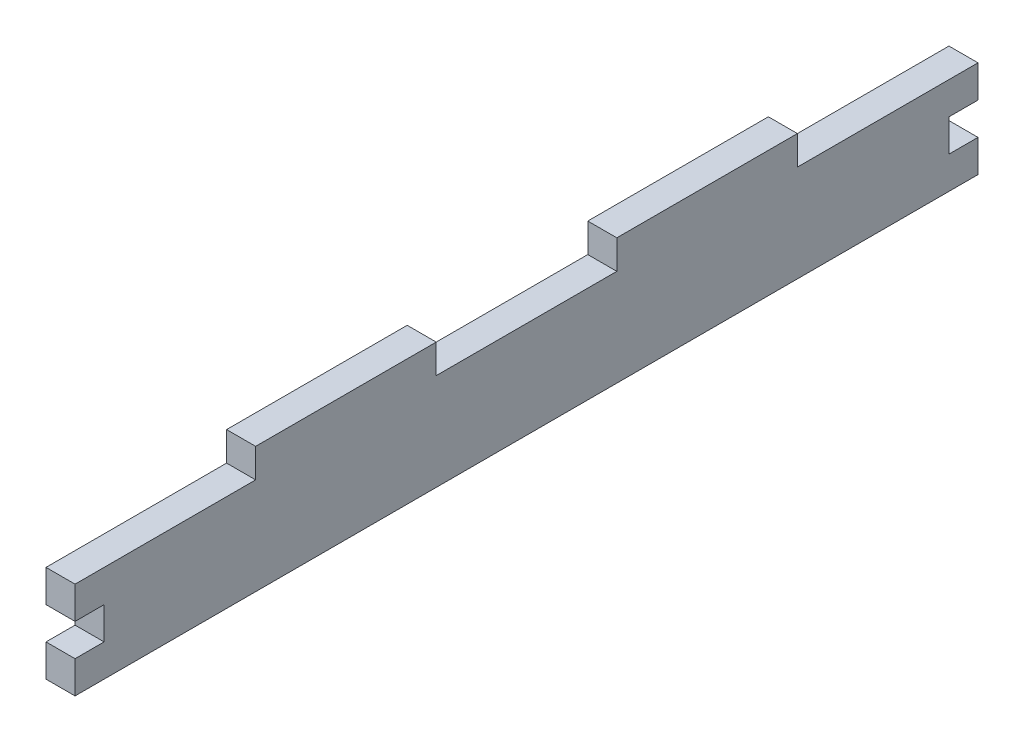
SolidWorks part; units mm, degrees
ref_plane "Front Plane" through (0, 0, 0) normal (0, 0, 1) x (1, 0, 0)
ref_plane "Top Plane" through (0, 0, 0) normal (0, 1, 0) x (1, 0, 0)
ref_plane "Right Plane" through (0, 0, 0) normal (1, 0, 0) x (0, 0, -1)
sketch "Sketch1" plane through (0, 0, 0) normal (0, 1, 0) x (1, 0, 0)
  line L1 (-207.5, -63.25) -> (207.5, -63.25)
  line L2 (-207.5, -63.25) -> (-207.5, 63.25)
  line L3 (-207.5, 63.25) -> (207.5, 63.25)
  line L4 (207.5, -63.25) -> (207.5, 63.25)
  line L5 (-207.5, -63.25) -> (207.5, 63.25) construction
  line L6 (-207.5, 63.25) -> (207.5, -63.25) construction
  point P0 (0, 0)
  dimension "D1" = 126.5
  dimension "D2" = 415
extrude "Boss-Extrude1" add sketch "Sketch1" along normal blind 6
sketch "Sketch2" plane through (0, 6, 0) normal (0, 1, 0) x (1, 0, 0)
  line L0 (213.5, -69.25) -> (213.5, 69.25)
  line L3 (-213.5, -69.25) -> (213.5, -69.25)
  line L4 (207.5, -63.25) -> (207.5, 63.25)
  line L5 (207.5, 63.25) -> (-207.5, 63.25)
  line L6 (-207.5, 63.25) -> (-207.5, -63.25)
  line L7 (-207.5, -63.25) -> (207.5, -63.25)
  line L8 (207.5, -63.25) -> (207.5, 63.25)
  line L9 (207.5, 63.25) -> (-207.5, 63.25)
  line L10 (-207.5, 63.25) -> (-207.5, -63.25)
  line L11 (-207.5, -63.25) -> (207.5, -63.25)
  line L12 (231.5, -87.25) -> (231.5, 87.25)
  line L13 (231.5, 87.25) -> (-231.5, 87.25)
  line L14 (-231.5, 87.25) -> (-231.5, -87.25)
  line L15 (-231.5, -87.25) -> (231.5, -87.25)
  line L16 (237.5, -93.25) -> (237.5, 93.25)
  line L19 (-237.5, -93.25) -> (237.5, -93.25)
  line L20 (213.5, 69.25) -> (-213.5, 69.25) construction
  line L21 (-213.5, 69.25) -> (-213.5, -69.25) construction
  line L22 (-213.5, -69.25) -> (-213.5, -63.25)
  line L27 (152.5, 69.25) -> (91.5, 69.25)
  line L28 (152.5, 69.25) -> (152.5, 63.25)
  line L29 (152.5, 63.25) -> (91.5, 63.25)
  line L30 (91.5, 69.25) -> (91.5, 63.25)
  line L31 (91.5, 69.25) -> (30.5, 69.25)
  line L32 (91.5, 69.25) -> (91.5, 63.25)
  line L33 (91.5, 63.25) -> (30.5, 63.25)
  line L34 (30.5, 69.25) -> (30.5, 63.25)
  line L35 (30.5, 69.25) -> (-30.5, 69.25)
  line L36 (30.5, 69.25) -> (30.5, 63.25)
  line L37 (30.5, 63.25) -> (-30.5, 63.25)
  line L38 (-30.5, 69.25) -> (-30.5, 63.25)
  line L39 (-30.5, 69.25) -> (-91.5, 69.25)
  line L40 (-30.5, 69.25) -> (-30.5, 63.25)
  line L41 (-30.5, 63.25) -> (-91.5, 63.25)
  line L42 (-91.5, 69.25) -> (-91.5, 63.25)
  line L43 (-91.5, 69.25) -> (-152.5, 69.25)
  line L44 (-91.5, 69.25) -> (-91.5, 63.25)
  line L45 (-91.5, 63.25) -> (-152.5, 63.25)
  line L46 (-152.5, 69.25) -> (-152.5, 63.25)
  line L47 (-152.5, 69.25) -> (-213.5, 69.25)
  line L48 (-152.5, 69.25) -> (-152.5, 63.25)
  line L49 (-152.5, 63.25) -> (-213.5, 63.25)
  line L50 (-213.5, 69.25) -> (-213.5, 63.25)
  line L51 (-213.5, 63.25) -> (-207.5, 63.25)
  line L52 (-213.5, 63.25) -> (-213.5, 37.95)
  line L53 (-213.5, 37.95) -> (-207.5, 37.95)
  line L54 (-207.5, 63.25) -> (-207.5, 37.95)
  line L55 (-207.5, 37.95) -> (-213.5, 37.95)
  line L56 (-207.5, 37.95) -> (-207.5, 12.65)
  line L57 (-207.5, 12.65) -> (-213.5, 12.65)
  line L58 (-213.5, 37.95) -> (-213.5, 12.65)
  line L59 (-213.5, 12.65) -> (-207.5, 12.65)
  line L60 (-213.5, 12.65) -> (-213.5, -12.65)
  line L61 (-213.5, -12.65) -> (-207.5, -12.65)
  line L62 (-207.5, 12.65) -> (-207.5, -12.65)
  line L63 (-207.5, -12.65) -> (-213.5, -12.65)
  line L64 (-207.5, -12.65) -> (-207.5, -37.95)
  line L65 (-207.5, -37.95) -> (-213.5, -37.95)
  line L66 (-213.5, -12.65) -> (-213.5, -37.95)
  line L67 (-213.5, -37.95) -> (-207.5, -37.95)
  line L68 (-213.5, -37.95) -> (-213.5, -63.25)
  line L69 (-213.5, -63.25) -> (-207.5, -63.25)
  line L70 (-207.5, -37.95) -> (-207.5, -63.25)
  line L71 (152.5, 63.25) -> (213.5, 63.25)
  line L72 (152.5, 63.25) -> (152.5, 69.25)
  line L73 (152.5, 69.25) -> (213.5, 69.25)
  line L74 (213.5, 63.25) -> (213.5, 69.25)
  line L75 (-237.5, 93.25) -> (-231.5, 93.25)
  line L76 (-237.5, 93.25) -> (-237.5, 55.95)
  line L77 (-237.5, 55.95) -> (-231.5, 55.95)
  line L78 (-231.5, 93.25) -> (-231.5, 55.95)
  line L79 (-237.5, 93.25) -> (-237.5, -93.25) construction
  line L80 (-231.5, 55.95) -> (-237.5, 55.95)
  line L81 (-231.5, 55.95) -> (-231.5, 18.65)
  line L82 (-231.5, 18.65) -> (-237.5, 18.65)
  line L83 (-237.5, 55.95) -> (-237.5, 18.65)
  line L84 (-237.5, 18.65) -> (-231.5, 18.65)
  line L85 (-237.5, 18.65) -> (-237.5, -18.65)
  line L86 (-237.5, -18.65) -> (-231.5, -18.65)
  line L87 (-231.5, 18.65) -> (-231.5, -18.65)
  line L88 (-231.5, -18.65) -> (-237.5, -18.65)
  line L89 (-231.5, -18.65) -> (-231.5, -55.95)
  line L90 (-231.5, -55.95) -> (-237.5, -55.95)
  line L91 (-237.5, -18.65) -> (-237.5, -55.95)
  line L92 (-237.5, -55.95) -> (-231.5, -55.95)
  line L93 (-237.5, -55.95) -> (-237.5, -93.25)
  line L94 (-237.5, -93.25) -> (-231.5, -93.25)
  line L95 (-231.5, -55.95) -> (-231.5, -93.25)
  line L96 (231.5, 87.25) -> (165.3571, 87.25)
  line L97 (231.5, 87.25) -> (231.5, 93.25)
  line L98 (231.5, 93.25) -> (165.3571, 93.25)
  line L99 (165.3571, 87.25) -> (165.3571, 93.25)
  line L100 (165.3571, 93.25) -> (99.2143, 93.25)
  line L101 (165.3571, 93.25) -> (165.3571, 87.25)
  line L102 (165.3571, 87.25) -> (99.2143, 87.25)
  line L103 (99.2143, 93.25) -> (99.2143, 87.25)
  line L104 (99.2143, 87.25) -> (33.0714, 87.25)
  line L105 (99.2143, 87.25) -> (99.2143, 93.25)
  line L106 (99.2143, 93.25) -> (33.0714, 93.25)
  line L107 (33.0714, 87.25) -> (33.0714, 93.25)
  line L108 (33.0714, 93.25) -> (-33.0714, 93.25)
  line L109 (33.0714, 93.25) -> (33.0714, 87.25)
  line L110 (33.0714, 87.25) -> (-33.0714, 87.25)
  line L111 (-33.0714, 93.25) -> (-33.0714, 87.25)
  line L112 (-33.0714, 87.25) -> (-99.2143, 87.25)
  line L113 (-33.0714, 87.25) -> (-33.0714, 93.25)
  line L114 (-33.0714, 93.25) -> (-99.2143, 93.25)
  line L115 (-99.2143, 87.25) -> (-99.2143, 93.25)
  line L116 (-99.2143, 93.25) -> (-165.3571, 93.25)
  line L117 (-99.2143, 93.25) -> (-99.2143, 87.25)
  line L118 (-99.2143, 87.25) -> (-165.3571, 87.25)
  line L119 (-165.3571, 93.25) -> (-165.3571, 87.25)
  line L120 (-165.3571, 87.25) -> (-231.5, 87.25)
  line L121 (-165.3571, 87.25) -> (-165.3571, 93.25)
  line L122 (-165.3571, 93.25) -> (-231.5, 93.25)
  line L123 (-231.5, 87.25) -> (-231.5, 93.25)
  line L124 (237.5, 93.25) -> (-237.5, 93.25) construction
  line L125 (237.5, 93.25) -> (231.5, 93.25)
  dimension "D1" = 0
  dimension "D2" = 6
  dimension "D3" = 18
  dimension "D4" = 6
extrude "Boss-Extrude2" add sketch "Sketch2" against normal blind 20 contours L78 L75 L76 L77 L14 | L77 L83 L82 L14 | L85 L86 L14 L82 | L86 L91 L90 L14 | L95 L14 L90 L93 L19 region at (-234.5, 6, 74.6) region at (-234.5, 6, 37.3) region at (-234.5, 6, 0) region at (-234.5, 6, -37.3) region at (-234.5, 6, -74.6)
extrude "Cut-Extrude1" cut sketch "Sketch1<2>" against normal through all both and the other way through all
sketch "Sketch1<2>" plane through (0, 0, 0) normal (0, 1, 0) x (1, 0, 0) same geometry as "Sketch1"
extrude "Boss-Extrude3" add sketch "Sketch2<4>" along normal blind 6 contours L77 L83 L82 L14 | L86 L91 L90 L14 region at (-234.5, 6, 37.3) region at (-234.5, 6, -37.3)
sketch "Sketch2<4>" plane through (0, 6, 0) normal (0, 1, 0) x (1, 0, 0) same geometry as "Sketch2"
sketch "Sketch5" plane through (0, 0, 93.25) normal (0, 0, 1) x (1, 0, 0)
  line L0 (-237.5, -14) -> (-237.5, 6) construction
  line L1 (-231.5, -14) -> (-237.5, -14)
  line L2 (-231.5, -14) -> (-231.5, -7.3333)
  line L3 (-231.5, -7.3333) -> (-237.5, -7.3333)
  line L4 (-237.5, -14) -> (-237.5, -7.3333)
  line L5 (-231.5, -14) -> (-231.5, 6) construction
  line L6 (-237.5, -7.3333) -> (-231.5, -7.3333)
  line L7 (-237.5, -7.3333) -> (-237.5, -0.6667)
  line L8 (-237.5, -0.6667) -> (-231.5, -0.6667)
  line L9 (-231.5, -7.3333) -> (-231.5, -0.6667)
  line L11 (-231.5, -0.6667) -> (-237.5, -0.6667)
  line L12 (-231.5, -0.6667) -> (-231.5, 6)
  line L13 (-231.5, 6) -> (-237.5, 6)
  line L14 (-237.5, -0.6667) -> (-237.5, 6)
  line M11 (-237.5, 6) -> (-237.5, -14)
  line M13 (-231.5, -14) -> (-231.5, 6)
extrude "Cut-Extrude3" cut sketch "Sketch5" against normal blind 6 contours L8 L3 M11 M13 region at (-234.5, -4, 93.25)
mirror "Mirror3" about plane through (0, 0, 0) normal (0, 0, 1) of "Cut-Extrude3"
